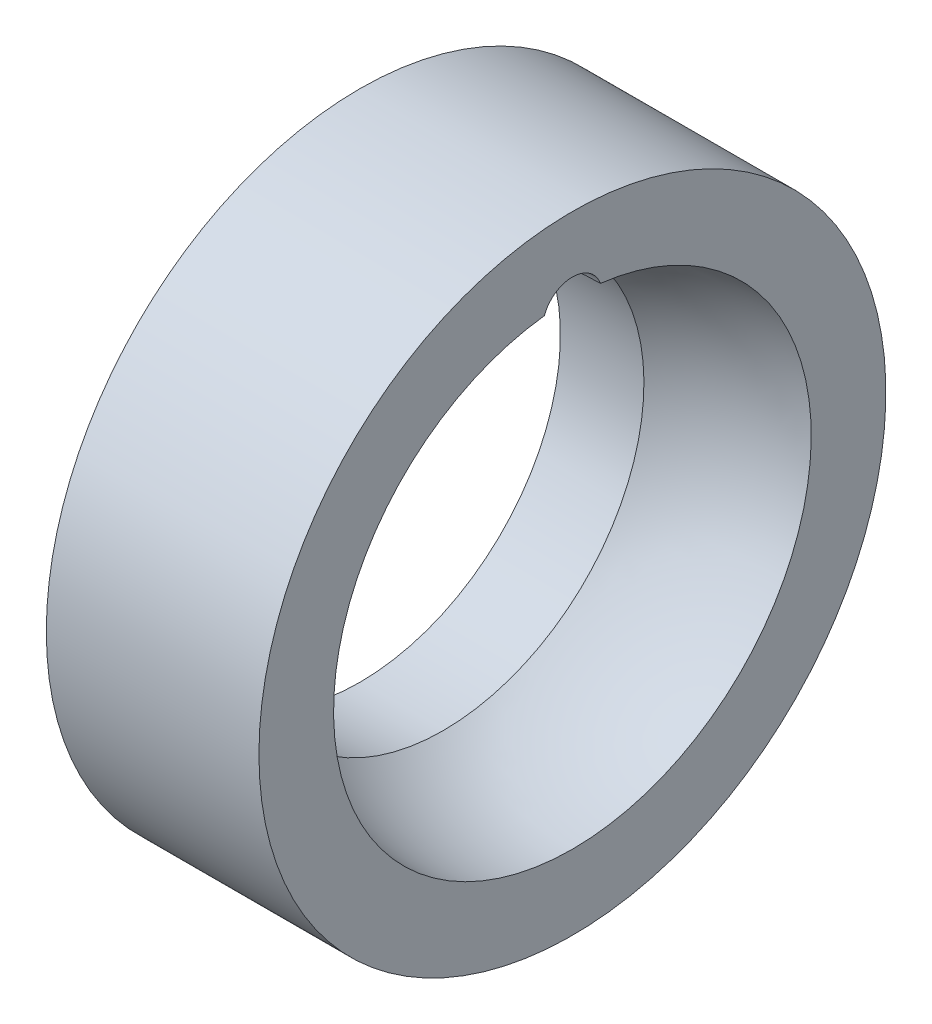
SolidWorks part; units mm, degrees
ref_plane "Front Plane" through (0, 0, 0) normal (0, 0, 1) x (1, 0, 0)
ref_plane "Top Plane" through (0, 0, 0) normal (0, 1, 0) x (1, 0, 0)
ref_plane "Right Plane" through (0, 0, 0) normal (1, 0, 0) x (0, 0, -1)
sketch "Sketch1" plane through (0, 0, 0) normal (0, 0, 1) x (1, 0, 0)
  line L0 (-142.8218, 0) -> (89.1089, 0) construction
  line L1 (-95.0495, 12.5) -> (-28.3684, 12.5)
  line L7 (-19.8779, 0) -> (-95.0495, 0)
  line L8 (-95.0495, 0) -> (-95.0495, 12.5)
  line L9 (20.0439, 40) -> (20.0439, 52.5)
  line L10 (-28.3684, 12.5) -> (-28.3684, 52.5)
  line L11 (-28.3684, 52.5) -> (20.0439, 52.5)
  arc A3 (20.0439, 40) -> (-19.8779, 0) centre (20.1221, 0.0001) ccw
  point P5 (20.0439, 0)
  point P6 (56.8976, 11.2673)
  point P13 (66.4606, 14.191)
  dimension "D6" = 28.3684
  dimension "D3" = 12.5
  dimension "D2" = 40
  dimension "D1" = 25
  dimension "D4" = 52.5
  dimension "D5" = 19.8779
  dimension "D7" = 20.0439
  dimension "D8" = 40
  dimension "D9" = 20.0439
revolve "Revolve1" add sketch "Sketch1" angle 360 about L0
sketch "Sketch2" plane through (20.0439, 0, 0) normal (1, 0, 0) x (0, 0, -1)
  line L0 (0, 0) -> (0, 54.3222) construction
  circle A0 centre (0, 38) radius 5
  point P5 (0, 0)
  point P6 (0, 0)
  dimension "D1" = 10
  dimension "D2" = 38
sketch "Sketch3" plane through (0, 0, 0) normal (0, 0, 1) x (1, 0, 0)
  line L0 (20.0439, -52.5) -> (20.0439, 52.5) construction
  arc A0 (20.0439, 38) -> (-12.3289, 19.8998) centre (20.0439, 0) ccw
  point P2 (0, 0)
sweep "Cut-Sweep1" cut profiles "Sketch2" path "Sketch3"
fillet "Fillet4" radius 2 rebuild error yes
fillet "Fillet5" radius 5 rebuild error yes
pattern_circular "CirPattern5" count 6 over 360 rebuild error yes
sketch "Sketch4" plane through (0, 0, 0) normal (0, 0, 1) x (1, 0, 0)
  line L0 (-95.0495, 0) -> (22.1666, 0) construction
  line L1 (-95.0495, 12.5) -> (-95.0495, -12.5) construction
  arc A0 (20.0439, 40) -> (-14.0604, 20.902) centre (20.0439, 0) ccw
  arc A2 (20.0439, -40) -> (-14.0604, -20.902) centre (20.0439, 0) cw
  dimension "D1" = 80
  dimension "D2" = 40
  dimension "D3" = 20.0439
sketch "Sketch6" plane through (20.0439, 0, 0) normal (1, 0, 0) x (0, 0, -1)
  line L0 (-34.641, -20) -> (34.641, 20)
ref_plane "Plane1" through (0, 0, 0) normal (0, -0.866, -0.5) x (0, 0.5, -0.866)
sketch "Sketch7" plane through (0, 0, 0) normal (0, -0.866, -0.5) x (0, 0.5, -0.866)
  line L0 (0, 27.7316) -> (0, -10.2469) construction
  arc A0 (-40, 20.0439) -> (-19.0599, -15.1231) centre (0, 20.0439) ccw
  arc A1 (40, 20.0439) -> (19.0599, -15.1231) centre (0, 20.0439) cw
  dimension "D1" = 80
sketch "Sketch8" plane through (0, 0, 0) normal (0, 0, 1) x (1, 0, 0)
  line L1 (-118.2194, 86.2959) -> (-15.5635, 86.2959)
  line L2 (-118.2194, 86.2959) -> (-118.2194, -90.3977)
  line L3 (-118.2194, -90.3977) -> (-15.5635, -90.3977)
  line L4 (-15.5635, 86.2959) -> (-15.5635, -90.3977)
extrude "Cut-Extrude1" cut sketch "Sketch8" against normal through all both and the other way through all
sketch "Sketch9" plane through (-15.5635, 0, 0) normal (-1, 0, 0) x (0, 0, 1)
  circle A0 centre (0, 0) radius 33.6032
extrude "Cut-Extrude2" cut sketch "Sketch9" against normal through all
